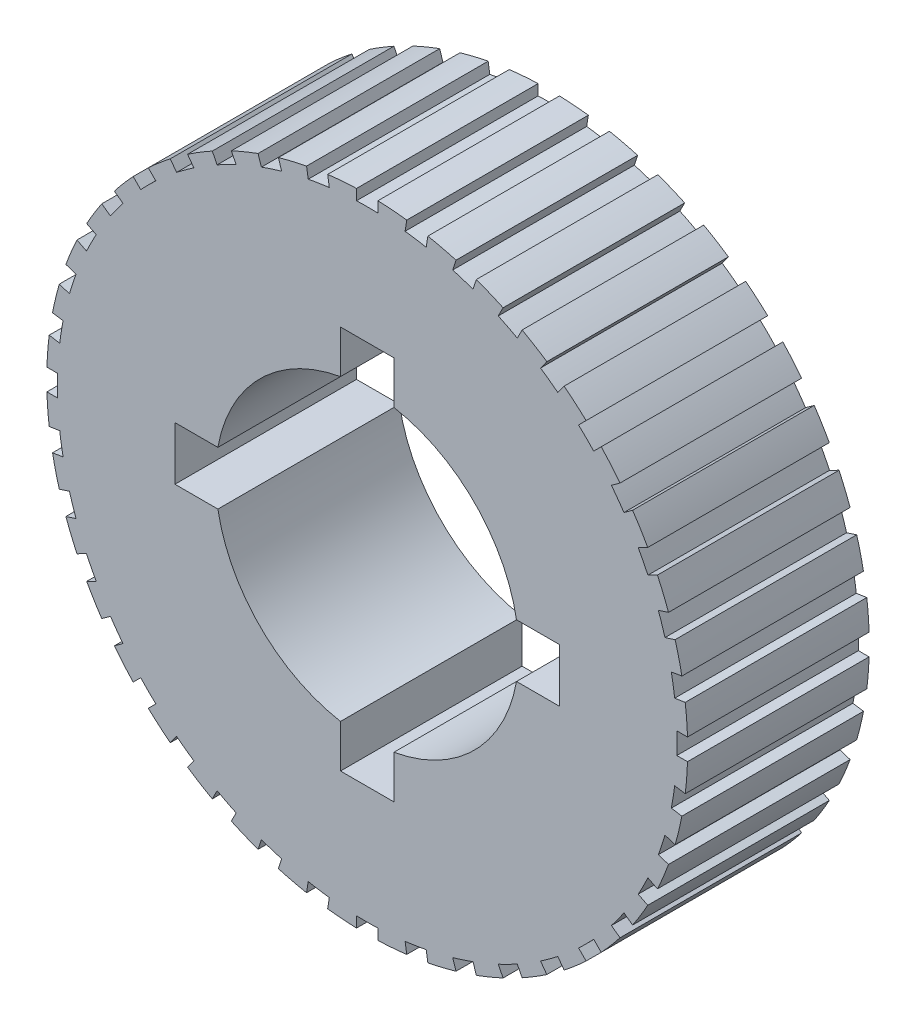
SolidWorks part; units mm, degrees
ref_plane "Plano frontal" through (0, 0, 0) normal (0, 0, 1) x (1, 0, 0)
ref_plane "Plano superior" through (0, 0, 0) normal (0, 1, 0) x (1, 0, 0)
ref_plane "Plano direito" through (0, 0, 0) normal (1, 0, 0) x (0, 0, -1)
sketch "Esboço1" plane through (0, 0, 0) normal (0, 0, 1) x (1, 0, 0)
  circle A0 centre (0, 0) radius 30
  circle A1 centre (0, 0) radius 10.7
  circle A2 centre (0, 0) radius 6.1
  circle A3 centre (0, 0) radius 8.9
  circle A4 centre (0, 0) radius 4.3
  dimension "D1" = 60
extrude "Ressalto-extrusão1" add sketch "Esboço1" along normal blind 30 contours A0 A1 region at (-29.1515, 0, 0)
sketch "Esboço2" plane through (0, 0, 0) normal (0, 0, -1) x (-1, 0, 0)
  circle A1 centre (0, 0) radius 10.7 construction
  circle A3 centre (0, 0) radius 10.7
  circle A4 centre (0, 0) radius 14.2
  dimension "D1" = 28.4
extrude "Corte-extrusão1" cut sketch "Esboço2" against normal through all
sketch "Esboço4" plane through (0, 0, 0) normal (0, 1, 0) x (1, 0, 0)
  line L0 (-29, -8.5) -> (-29, -9.5)
  line L2 (-30, -2) -> (-30, -3)
  line L4 (0, 0) -> (0, 11.1523) construction
  line L6 (-29, -29) -> (-30, -29)
  line L7 (-30, -8.5) -> (-30, -9.5)
  line L8 (-29, -35.5) -> (-30, -35.5)
  line L9 (-30, -35.5) -> (-30, -34.5)
  line L10 (-30, -34.5) -> (-29, -34.5)
  line L11 (-30, -29) -> (-30, -28)
  line L12 (-30, -28) -> (-29, -28)
  line L14 (-29, -22.5) -> (-30, -22.5)
  line L15 (-30, -22.5) -> (-30, -21.5)
  line L16 (-30, -21.5) -> (-29, -21.5)
  line L17 (-29, -28) -> (-29, -29)
  line L18 (-29, -16) -> (-30, -16)
  line L19 (-30, -16) -> (-30, -15)
  line L20 (-30, -15) -> (-29, -15)
  line L21 (-29, -21.5) -> (-29, -22.5)
  line L22 (-29, -9.5) -> (-30, -9.5)
  line L23 (-30, -9.5) -> (-30, -8.5)
  line L24 (-30, -8.5) -> (-29, -8.5)
  line L25 (-29, -15) -> (-29, -16)
  line L26 (-29, -3) -> (-30, -3)
  line L27 (-30, -3) -> (-30, -2)
  line L28 (-30, -2) -> (-29, -2)
  line L30 (-29, -2) -> (-29, -3)
  line L31 (-30, -15) -> (-30, -16)
  line L32 (-29, -34.5) -> (-29, -35.5)
  line L33 (-30, 4.5) -> (-29, 4.5)
  line L34 (-30, 3.5) -> (-30, 4.5)
  line L35 (-29, 3.5) -> (-30, 3.5)
  line L37 (-30, -21.5) -> (-30, -22.5)
  line L38 (-30, -28) -> (-30, -29)
  line L39 (-30, -34.5) -> (-30, -35.5)
  point P0 (0, 0)
  dimension "D1" = 7
  dimension "D2" = 29
  dimension "D3" = 30
  dimension "D4" = 2
  dimension "D5" = 3
  dimension "D6" = 8.5
sketch "Esboço5" plane through (0, 0, 30) normal (0, 0, 1) x (1, 0, 0)
  line L0 (0, 0) -> (-39.2966, 0) construction
  line L5 (-1, 29.9833) -> (-1, 28.9828)
  line L6 (1, 29.9833) -> (1, 28.9828)
  arc A3 (1, 29.9833) -> (-1, 29.9833) centre (0, 0) ccw
  arc A4 (1, 28.9828) -> (-1, 28.9828) centre (0, 0) ccw
fillet "Filete2" radius 2 2 edges at (30, 0, 0) (30, 0, 30) second distance 3 first distance on face at (-14.2, 0, 0) first distance on face at (30, 0, 30)
sketch "Esboço6" plane through (0, 0, 30) normal (0, 0, 1) x (1, 0, 0)
  line L0 (5.5216, 28.4695) -> (5.6781, 29.4577)
  line L1 (3.7027, 29.7706) -> (3.5462, 28.7824)
  line L2 (-1, 29.9833) -> (-1, 28.9828)
  line L3 (1, 28.9828) -> (1, 29.9833)
  line L4 (-1, 29.9833) -> (-1, 28.9828)
  line L5 (1, 28.9828) -> (1, 29.9833)
  line L6 (9.9072, 27.2552) -> (10.2164, 28.2068)
  line L7 (8.3143, 28.8249) -> (8.0051, 27.8733)
  line L8 (14.0489, 25.3698) -> (14.5032, 26.2614)
  line L9 (12.7211, 27.1693) -> (12.2669, 26.2778)
  line L10 (17.8447, 22.8598) -> (18.4328, 23.6692)
  line L11 (16.8147, 24.8448) -> (16.2266, 24.0353)
  line L12 (21.201, 19.7868) -> (21.9085, 20.4943)
  line L13 (20.4943, 21.9085) -> (19.7868, 21.201)
  line L14 (24.0353, 16.2266) -> (24.8448, 16.8147)
  line L15 (23.6692, 18.4328) -> (22.8598, 17.8447)
  line L16 (26.2778, 12.2669) -> (27.1693, 12.7211)
  line L17 (26.2614, 14.5032) -> (25.3698, 14.0489)
  line L18 (27.8733, 8.0051) -> (28.8249, 8.3143)
  line L19 (28.2068, 10.2164) -> (27.2552, 9.9072)
  line L20 (28.7824, 3.5462) -> (29.7706, 3.7027)
  line L21 (29.4577, 5.6781) -> (28.4695, 5.5216)
  line L22 (28.9828, -1) -> (29.9833, -1)
  line L23 (29.9833, 1) -> (28.9828, 1)
  line L24 (28.4695, -5.5216) -> (29.4577, -5.6781)
  line L25 (29.7706, -3.7027) -> (28.7824, -3.5462)
  line L26 (27.2552, -9.9072) -> (28.2068, -10.2164)
  line L27 (28.8249, -8.3143) -> (27.8733, -8.0051)
  line L28 (25.3698, -14.0489) -> (26.2614, -14.5032)
  line L29 (27.1693, -12.7211) -> (26.2778, -12.2669)
  line L30 (22.8598, -17.8447) -> (23.6692, -18.4328)
  line L31 (24.8448, -16.8147) -> (24.0353, -16.2266)
  line L32 (19.7868, -21.201) -> (20.4943, -21.9085)
  line L33 (21.9085, -20.4943) -> (21.201, -19.7868)
  line L34 (16.2266, -24.0353) -> (16.8147, -24.8448)
  line L35 (18.4328, -23.6692) -> (17.8447, -22.8598)
  line L36 (12.2669, -26.2778) -> (12.7211, -27.1693)
  line L37 (14.5032, -26.2614) -> (14.0489, -25.3698)
  line L38 (8.0051, -27.8733) -> (8.3143, -28.8249)
  line L39 (10.2164, -28.2068) -> (9.9072, -27.2552)
  line L40 (3.5462, -28.7824) -> (3.7027, -29.7706)
  line L41 (5.6781, -29.4577) -> (5.5216, -28.4695)
  line L42 (-1, -28.9828) -> (-1, -29.9833)
  line L43 (1, -29.9833) -> (1, -28.9828)
  line L44 (-5.5216, -28.4695) -> (-5.6781, -29.4577)
  line L45 (-3.7027, -29.7706) -> (-3.5462, -28.7824)
  line L46 (-9.9072, -27.2552) -> (-10.2164, -28.2068)
  line L47 (-8.3143, -28.8249) -> (-8.0051, -27.8733)
  line L48 (-14.0489, -25.3698) -> (-14.5032, -26.2614)
  line L49 (-12.7211, -27.1693) -> (-12.2669, -26.2778)
  line L50 (-17.8447, -22.8598) -> (-18.4328, -23.6692)
  line L51 (-16.8147, -24.8448) -> (-16.2266, -24.0353)
  line L52 (-21.201, -19.7868) -> (-21.9085, -20.4943)
  line L53 (-20.4943, -21.9085) -> (-19.7868, -21.201)
  line L54 (-24.0353, -16.2266) -> (-24.8448, -16.8147)
  line L55 (-23.6692, -18.4328) -> (-22.8598, -17.8447)
  line L56 (-26.2778, -12.2669) -> (-27.1693, -12.7211)
  line L57 (-26.2614, -14.5032) -> (-25.3698, -14.0489)
  line L58 (-27.8733, -8.0051) -> (-28.8249, -8.3143)
  line L59 (-28.2068, -10.2164) -> (-27.2552, -9.9072)
  line L60 (-28.7824, -3.5462) -> (-29.7706, -3.7027)
  line L61 (-29.4577, -5.6781) -> (-28.4695, -5.5216)
  line L62 (-28.9828, 1) -> (-29.9833, 1)
  line L63 (-29.9833, -1) -> (-28.9828, -1)
  line L64 (-28.4695, 5.5216) -> (-29.4577, 5.6781)
  line L65 (-29.7706, 3.7027) -> (-28.7824, 3.5462)
  line L66 (-27.2552, 9.9072) -> (-28.2068, 10.2164)
  line L67 (-28.8249, 8.3143) -> (-27.8733, 8.0051)
  line L68 (-25.3698, 14.0489) -> (-26.2614, 14.5032)
  line L69 (-27.1693, 12.7211) -> (-26.2778, 12.2669)
  line L70 (-22.8598, 17.8447) -> (-23.6692, 18.4328)
  line L71 (-24.8448, 16.8147) -> (-24.0353, 16.2266)
  line L72 (-19.7868, 21.201) -> (-20.4943, 21.9085)
  line L73 (-21.9085, 20.4943) -> (-21.201, 19.7868)
  line L74 (-16.2266, 24.0353) -> (-16.8147, 24.8448)
  line L75 (-18.4328, 23.6692) -> (-17.8447, 22.8598)
  line L76 (-12.2669, 26.2778) -> (-12.7211, 27.1693)
  line L77 (-14.5032, 26.2614) -> (-14.0489, 25.3698)
  line L78 (-8.0051, 27.8733) -> (-8.3143, 28.8249)
  line L79 (-10.2164, 28.2068) -> (-9.9072, 27.2552)
  line L80 (-3.5462, 28.7824) -> (-3.7027, 29.7706)
  line L81 (-5.6781, 29.4577) -> (-5.5216, 28.4695)
  arc A0 (5.5216, 28.4695) -> (3.5462, 28.7824) centre (0, 0) ccw
  arc A1 (5.6781, 29.4577) -> (3.7027, 29.7706) centre (0, 0) ccw
  arc A2 (1, 28.9828) -> (-1, 28.9828) centre (0, 0) ccw
  arc A3 (1, 29.9833) -> (-1, 29.9833) centre (0, 0) ccw
  arc A4 (1, 28.9828) -> (-1, 28.9828) centre (0, 0) ccw
  arc A5 (1, 29.9833) -> (-1, 29.9833) centre (0, 0) ccw
  arc A6 (9.9072, 27.2552) -> (8.0051, 27.8733) centre (0, 0) ccw
  arc A7 (10.2164, 28.2068) -> (8.3143, 28.8249) centre (0, 0) ccw
  arc A8 (14.0489, 25.3698) -> (12.2669, 26.2778) centre (0, 0) ccw
  arc A9 (14.5032, 26.2614) -> (12.7211, 27.1693) centre (0, 0) ccw
  arc A10 (17.8447, 22.8598) -> (16.2266, 24.0353) centre (0, 0) ccw
  arc A11 (18.4328, 23.6692) -> (16.8147, 24.8448) centre (0, 0) ccw
  arc A12 (21.201, 19.7868) -> (19.7868, 21.201) centre (0, 0) ccw
  arc A13 (21.9085, 20.4943) -> (20.4943, 21.9085) centre (0, 0) ccw
  arc A14 (24.0353, 16.2266) -> (22.8598, 17.8447) centre (0, 0) ccw
  arc A15 (24.8448, 16.8147) -> (23.6692, 18.4328) centre (0, 0) ccw
  arc A16 (26.2778, 12.2669) -> (25.3698, 14.0489) centre (0, 0) ccw
  arc A17 (27.1693, 12.7211) -> (26.2614, 14.5032) centre (0, 0) ccw
  arc A18 (27.8733, 8.0051) -> (27.2552, 9.9072) centre (0, 0) ccw
  arc A19 (28.8249, 8.3143) -> (28.2068, 10.2164) centre (0, 0) ccw
  arc A20 (28.7824, 3.5462) -> (28.4695, 5.5216) centre (0, 0) ccw
  arc A21 (29.7706, 3.7027) -> (29.4577, 5.6781) centre (0, 0) ccw
  arc A22 (28.9828, -1) -> (28.9828, 1) centre (0, 0) ccw
  arc A23 (29.9833, -1) -> (29.9833, 1) centre (0, 0) ccw
  arc A24 (28.4695, -5.5216) -> (28.7824, -3.5462) centre (0, 0) ccw
  arc A25 (29.4577, -5.6781) -> (29.7706, -3.7027) centre (0, 0) ccw
  arc A26 (27.2552, -9.9072) -> (27.8733, -8.0051) centre (0, 0) ccw
  arc A27 (28.2068, -10.2164) -> (28.8249, -8.3143) centre (0, 0) ccw
  arc A28 (25.3698, -14.0489) -> (26.2778, -12.2669) centre (0, 0) ccw
  arc A29 (26.2614, -14.5032) -> (27.1693, -12.7211) centre (0, 0) ccw
  arc A30 (22.8598, -17.8447) -> (24.0353, -16.2266) centre (0, 0) ccw
  arc A31 (23.6692, -18.4328) -> (24.8448, -16.8147) centre (0, 0) ccw
  arc A32 (19.7868, -21.201) -> (21.201, -19.7868) centre (0, 0) ccw
  arc A33 (20.4943, -21.9085) -> (21.9085, -20.4943) centre (0, 0) ccw
  arc A34 (16.2266, -24.0353) -> (17.8447, -22.8598) centre (0, 0) ccw
  arc A35 (16.8147, -24.8448) -> (18.4328, -23.6692) centre (0, 0) ccw
  arc A36 (12.2669, -26.2778) -> (14.0489, -25.3698) centre (0, 0) ccw
  arc A37 (12.7211, -27.1693) -> (14.5032, -26.2614) centre (0, 0) ccw
  arc A38 (8.0051, -27.8733) -> (9.9072, -27.2552) centre (0, 0) ccw
  arc A39 (8.3143, -28.8249) -> (10.2164, -28.2068) centre (0, 0) ccw
  arc A40 (3.5462, -28.7824) -> (5.5216, -28.4695) centre (0, 0) ccw
  arc A41 (3.7027, -29.7706) -> (5.6781, -29.4577) centre (0, 0) ccw
  arc A42 (-1, -28.9828) -> (1, -28.9828) centre (0, 0) ccw
  arc A43 (-1, -29.9833) -> (1, -29.9833) centre (0, 0) ccw
  arc A44 (-5.5216, -28.4695) -> (-3.5462, -28.7824) centre (0, 0) ccw
  arc A45 (-5.6781, -29.4577) -> (-3.7027, -29.7706) centre (0, 0) ccw
  arc A46 (-9.9072, -27.2552) -> (-8.0051, -27.8733) centre (0, 0) ccw
  arc A47 (-10.2164, -28.2068) -> (-8.3143, -28.8249) centre (0, 0) ccw
  arc A48 (-14.0489, -25.3698) -> (-12.2669, -26.2778) centre (0, 0) ccw
  arc A49 (-14.5032, -26.2614) -> (-12.7211, -27.1693) centre (0, 0) ccw
  arc A50 (-17.8447, -22.8598) -> (-16.2266, -24.0353) centre (0, 0) ccw
  arc A51 (-18.4328, -23.6692) -> (-16.8147, -24.8448) centre (0, 0) ccw
  arc A52 (-21.201, -19.7868) -> (-19.7868, -21.201) centre (0, 0) ccw
  arc A53 (-21.9085, -20.4943) -> (-20.4943, -21.9085) centre (0, 0) ccw
  arc A54 (-24.0353, -16.2266) -> (-22.8598, -17.8447) centre (0, 0) ccw
  arc A55 (-24.8448, -16.8147) -> (-23.6692, -18.4328) centre (0, 0) ccw
  arc A56 (-26.2778, -12.2669) -> (-25.3698, -14.0489) centre (0, 0) ccw
  arc A57 (-27.1693, -12.7211) -> (-26.2614, -14.5032) centre (0, 0) ccw
  arc A58 (-27.8733, -8.0051) -> (-27.2552, -9.9072) centre (0, 0) ccw
  arc A59 (-28.8249, -8.3143) -> (-28.2068, -10.2164) centre (0, 0) ccw
  arc A60 (-28.7824, -3.5462) -> (-28.4695, -5.5216) centre (0, 0) ccw
  arc A61 (-29.7706, -3.7027) -> (-29.4577, -5.6781) centre (0, 0) ccw
  arc A62 (-28.9828, 1) -> (-28.9828, -1) centre (0, 0) ccw
  arc A63 (-29.9833, 1) -> (-29.9833, -1) centre (0, 0) ccw
  arc A64 (-28.4695, 5.5216) -> (-28.7824, 3.5462) centre (0, 0) ccw
  arc A65 (-29.4577, 5.6781) -> (-29.7706, 3.7027) centre (0, 0) ccw
  arc A66 (-27.2552, 9.9072) -> (-27.8733, 8.0051) centre (0, 0) ccw
  arc A67 (-28.2068, 10.2164) -> (-28.8249, 8.3143) centre (0, 0) ccw
  arc A68 (-25.3698, 14.0489) -> (-26.2778, 12.2669) centre (0, 0) ccw
  arc A69 (-26.2614, 14.5032) -> (-27.1693, 12.7211) centre (0, 0) ccw
  arc A70 (-22.8598, 17.8447) -> (-24.0353, 16.2266) centre (0, 0) ccw
  arc A71 (-23.6692, 18.4328) -> (-24.8448, 16.8147) centre (0, 0) ccw
  arc A72 (-19.7868, 21.201) -> (-21.201, 19.7868) centre (0, 0) ccw
  arc A73 (-20.4943, 21.9085) -> (-21.9085, 20.4943) centre (0, 0) ccw
  arc A74 (-16.2266, 24.0353) -> (-17.8447, 22.8598) centre (0, 0) ccw
  arc A75 (-16.8147, 24.8448) -> (-18.4328, 23.6692) centre (0, 0) ccw
  arc A76 (-12.2669, 26.2778) -> (-14.0489, 25.3698) centre (0, 0) ccw
  arc A77 (-12.7211, 27.1693) -> (-14.5032, 26.2614) centre (0, 0) ccw
  arc A78 (-8.0051, 27.8733) -> (-9.9072, 27.2552) centre (0, 0) ccw
  arc A79 (-8.3143, 28.8249) -> (-10.2164, 28.2068) centre (0, 0) ccw
  arc A80 (-3.5462, 28.7824) -> (-5.5216, 28.4695) centre (0, 0) ccw
  arc A81 (-3.7027, 29.7706) -> (-5.6781, 29.4577) centre (0, 0) ccw
  point P165 (0, 0)
  dimension "D1" = 0
  dimension "D2" = 40
extrude "Corte-extrusão2" cut sketch "Esboço6" against normal through all
sketch "Esboço7" plane through (0, 0, 0) normal (0, 0, -1) x (-1, 0, 0)
  line L0 (18, 0) -> (18, 2.5)
  line L1 (-200000, 0) -> (200039.2966, 0) construction
  line L2 (0, 18) -> (-2.5, 18)
  line L3 (0, 18) -> (2.5, 18)
  line L4 (-2.5, 18) -> (-2.5, 13.9782)
  line L5 (2.5, 18) -> (2.5, 13.9782)
  line L6 (-200000, 0) -> (200039.2966, 0)
  line L7 (0, 0) -> (-42.3655, 0) construction
  line L8 (2.5, -18) -> (2.5, -13.9782)
  line L9 (-2.5, -18) -> (-2.5, -13.9782)
  line L10 (0, -18) -> (2.5, -18)
  line L11 (0, -18) -> (-2.5, -18)
  line L12 (18, 0) -> (18, -2.5)
  line L13 (18, 2.5) -> (13.9782, 2.5)
  line L14 (18, -2.5) -> (13.9782, -2.5)
  line L15 (-18, -2.5) -> (-13.9782, -2.5)
  line L16 (-18, 2.5) -> (-13.9782, 2.5)
  line L17 (-18, 0) -> (-18, -2.5)
  line L18 (-18, 0) -> (-18, 2.5)
  line L19 (0, -18) -> (2.5, -18)
  line L20 (0, -18) -> (-2.5, -18)
  line L21 (2.5, -18) -> (2.5, -13.9782)
  line L22 (-2.5, -18) -> (-2.5, -13.9782)
  line L23 (-2.5, 18) -> (-2.5, 13.9782)
  line L24 (2.5, 18) -> (2.5, 13.9782)
  line L25 (0, 18) -> (-2.5, 18)
  line L26 (0, 18) -> (2.5, 18)
  line L27 (-18, 0) -> (-18, -2.5)
  line L28 (-18, 0) -> (-18, 2.5)
  line L29 (-18, -2.5) -> (-13.9782, -2.5)
  line L30 (-18, 2.5) -> (-13.9782, 2.5)
  line L31 (18, 2.5) -> (13.9782, 2.5)
  line L32 (18, -2.5) -> (13.9782, -2.5)
  line L33 (18, 0) -> (18, 2.5)
  line L34 (18, 0) -> (18, -2.5)
  circle A0 centre (0, 0) radius 14.2 construction
  arc A1 (-2.5, -13.9782) -> (2.5, -13.9782) centre (0, 0) ccw
  arc A2 (2.5, 13.9782) -> (-2.5, 13.9782) centre (0, 0) ccw
  arc A3 (-13.9782, 2.5) -> (-13.9782, -2.5) centre (0, 0) ccw
  arc A4 (13.9782, -2.5) -> (13.9782, 2.5) centre (0, 0) ccw
  arc A5 (2.5, 13.9782) -> (-2.5, 13.9782) centre (0, 0) ccw
  arc A6 (-2.5, -13.9782) -> (2.5, -13.9782) centre (0, 0) ccw
  arc A7 (13.9782, -2.5) -> (13.9782, 2.5) centre (0, 0) ccw
  arc A8 (-13.9782, 2.5) -> (-13.9782, -2.5) centre (0, 0) ccw
  point P49 (0, 0)
  dimension "D1" = 2.5
  dimension "D2" = 2.5
  dimension "D3" = 18
  dimension "D4" = 4
extrude "Corte-extrusão3" cut sketch "Esboço7" against normal through all contours A3 L15 L17 L18 L16 | A1 L8 L10 L11 L9 | L13 A4 L14 L12 L0 | L5 A2 L4 L2 L3
sketch "Esboço8" plane through (0, 0, 0) normal (0, 0, -1) x (-1, 0, 0)
  circle A0 centre (0, 0) radius 40
  dimension "D1" = 80
extrude "Corte-extrusão4" cut sketch "Esboço8" against normal blind 6.5
sketch "Esboço9" plane through (0, 0, 30) normal (0, 0, 1) x (1, 0, 0)
  circle A1 centre (0, 0) radius 40
  circle A2 centre (0, 0) radius 40
  dimension "D1" = 0
extrude "Corte-extrusão5" cut sketch "Esboço9" against normal blind 6.5
